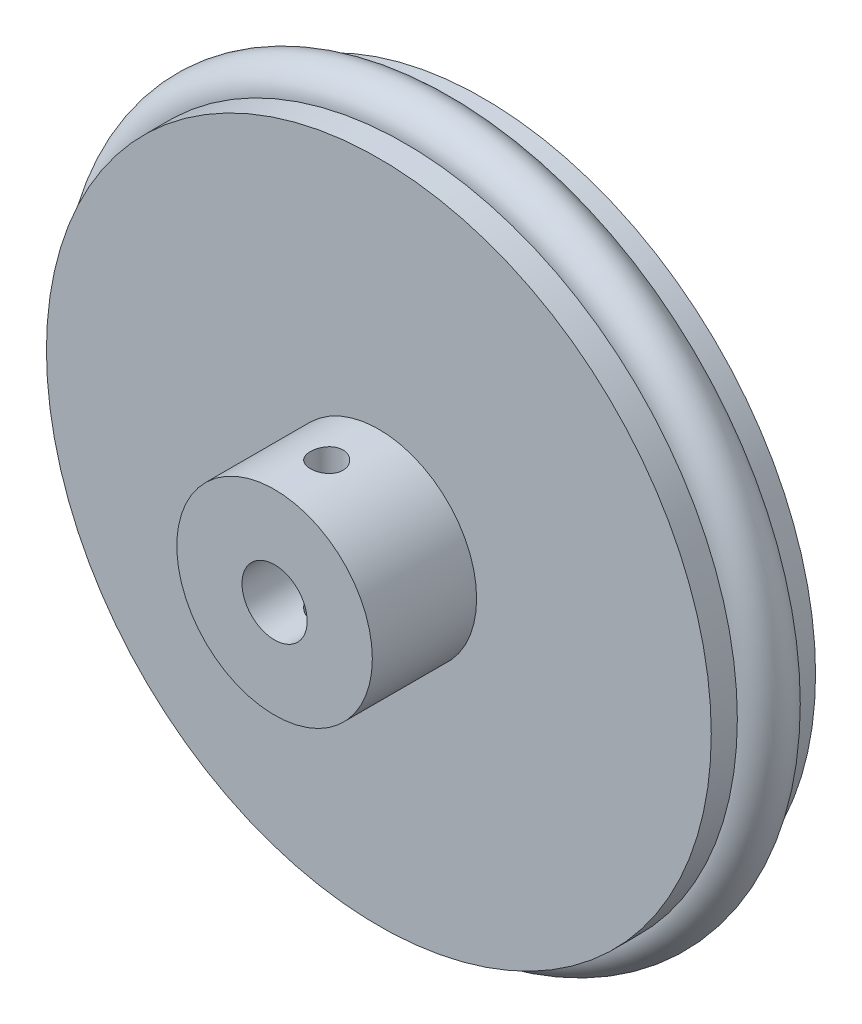
SolidWorks part; units mm, degrees
ref_plane "Спереди" through (0, 0, 0) normal (0, 0, 1) x (1, 0, 0)
ref_plane "Сверху" through (0, 0, 0) normal (0, 1, 0) x (1, 0, 0)
ref_plane "Справа" through (0, 0, 0) normal (1, 0, 0) x (0, 0, -1)
sketch "Эскиз1" plane through (0, 0, 0) normal (0, 0, 1) x (1, 0, 0)
  circle A0 centre (0, 0) radius 25.5
  circle A1 centre (0, 0) radius 2.5
  point P12 (0, 0)
  dimension "D1" = 51
  dimension "D2" = 5
extrude "Бобышка-Вытянуть1" add sketch "Эскиз1" along normal blind 8
sketch "Эскиз2" plane through (0, 0, 8) normal (0, 0, 1) x (1, 0, 0)
  line L0 (0, 0) -> (15.4302, 0) construction
  circle A3 centre (0, 0) radius 7.5
  circle A4 centre (0, 0) radius 2.5 construction
  circle A5 centre (0, 0) radius 2.5
  point P6 (2.5, 0)
  point P8 (7.5, 0)
  dimension "D2" = 15
  dimension "D3" = 5
extrude "Бобышка-Вытянуть2" add sketch "Эскиз2" along normal blind 8
sketch "Эскиз3" plane through (0, 0, 0) normal (1, 0, 0) x (0, 0, -1)
  circle A0 centre (-18, 0) radius 1.5
  dimension "D1" = 3
sketch "Эскиз4" plane through (0, 0, 0) normal (0, 1, 0) x (1, 0, 0)
  line L0 (-7.5, -16) -> (7.5, -16) construction
  circle A0 centre (0, -12) radius 1.25
  dimension "D2" = 2.5
  dimension "D1" = 4
extrude "Вырез-Вытянуть2" cut sketch "Эскиз4" against normal blind 10 and the other way blind 10
sketch "Эскиз5" plane through (0, 0, 0) normal (1, 0, 0) x (0, 0, -1)
  line L0 (0, 0) -> (-39.0671, 0) construction
  line L1 (-6, 25.5) -> (-2, 25.5)
  line L3 (0, -25.5) -> (0, 25.5) construction
  arc A0 (-6, 25.5) -> (-2, 25.5) centre (-4, 25.5) ccw
  dimension "D1" = 2
  dimension "D2" = 4
  dimension "D3" = 25.5
revolve "Вырез-Повернуть1" cut sketch "Эскиз5" angle 360 about L0
sketch "Эскиз6" plane through (0, 0, 0) normal (1, 0, 0) x (0, 0, -1)
  line L0 (0, 0) -> (-38.9769, 0) construction
  line L1 (0, -25.5) -> (0, 25.5) construction
  circle A0 centre (-4, 25.5) radius 2
revolve "Повернуть1" add sketch "Эскиз6" angle 360 about L0
